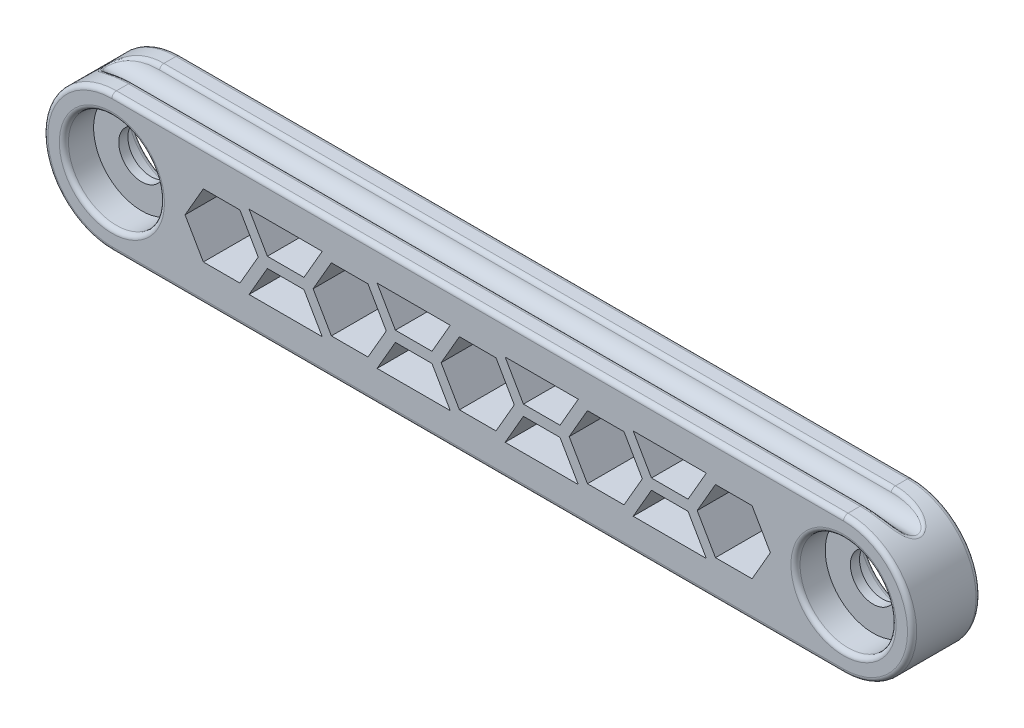
SolidWorks part; units mm, degrees
ref_plane "Front Plane" through (0, 0, 0) normal (0, 0, 1) x (1, 0, 0)
ref_plane "Top Plane" through (0, 0, 0) normal (0, 1, 0) x (1, 0, 0)
ref_plane "Right Plane" through (0, 0, 0) normal (1, 0, 0) x (0, 0, -1)
ref_axis "X" through (-88.99, 0, 0) along (1, 0, 0)
ref_axis "Y" through (0, 55, 0) along (0, -1, 0)
ref_axis "Z" through (0, 0, -88.99) along (0, 0, 1)
sketch "Sketch1" plane through (0, 0, 0) normal (0, 0, 1) x (1, 0, 0)
  line L0 (-80, 0) -> (80, 0) construction
  line L2 (-80, 15) -> (80, 15)
  line L3 (-80, -15) -> (80, -15)
  arc A0 (-80, 15) -> (-80, -15) centre (-80, 0) ccw
  arc A1 (80, -15) -> (80, 15) centre (80, 0) ccw
  circle A2 centre (80, 0) radius 10.5
  circle A3 centre (-80, 0) radius 10.5
  circle A4 centre (-80, 0) radius 5
  circle A5 centre (80, 0) radius 5
  point P5 (0, 0)
  dimension "D2" = 15
  dimension "D3" = 21
  dimension "D4" = 10
  dimension "D1" = 160
extrude "Boss-Extrude1" add sketch "Sketch1" along normal mid plane 2 contours L3 A1 L2 A0 A3 A2 | A4 A3 | A2 A5 region at (0, 0, 0) region at (69.797, 0, 0) region at (-90.203, 0, 0)
extrude "Boss-Extrude2" add sketch "Sketch1<3>" along normal mid plane 15 contours L3 A1 L2 A0 A3 A2 region at (0, 0, 0)
sketch "Sketch1<3>" plane through (0, 0, 0) normal (0, 0, 1) x (1, 0, 0) same geometry as "Sketch1"
sketch "Sketch2" plane through (0, 0, 0) normal (1, 0, 0) x (0, 0, -1)
  line L0 (-7.5, 15) -> (7.5, 15) construction
  line L1 (-7.5, 15) -> (7.5, 15)
  arc A0 (-3, 15) -> (3, 15) centre (0, 15) ccw
  point P6 (0, 15)
  dimension "D1" = 3
extrude "Cut-Extrude1" cut sketch "Sketch2" against normal through all both and the other way through all contours L1 A0 region at (0, 13.7268, 0)
fillet "Fillet1" radius 1 4 edges at (-88.9935, 12.0049, -0.1707) (0, 15, 3) (88.9935, 12.0049, 0.1707) (0, 15, -3)
mirror "Mirror3" [suppressed] about plane through (0, 0, 0) normal (0, 1, 0)
sketch "Sketch3" [suppressed] plane through (0, 0, 1) normal (0, 0, 1) x (1, 0, 0)
  circle A1 centre (80, 0) radius 11.1
  circle A2 centre (80, 0) radius 11.1
  circle A3 centre (80, 0) radius 5 construction
  circle A4 centre (80, 0) radius 5
  dimension "D1" = 0
extrude "Boss-Extrude3" [suppressed] add sketch "Sketch3" along normal up to surface (6.5 mm away) up to face at (90.5, 0, 7.5)
fillet "Fillet2" radius 1 12 edges at (-95, 0, 7.5) (0, 15, 7.5) (95, 0, 7.5) (0, -15, 7.5) (-69.5, 0, 7.5) (90.5, 0, 7.5) (95, 0, -7.5) (0, 15, -7.5) (-95, 0, -7.5) (0, -15, -7.5) (-69.5, 0, -7.5) (90.5, 0, -7.5)
mirror "Mirror1" [suppressed] about plane through (0, 0, 0) normal (1, 0, 0) of bodies 104
delete or keep bodies "Body-Delete/Keep 1" [suppressed] type keep bodies bodies 105
sketch "Sketch4" [suppressed] plane through (0, 0, 7.5) normal (0, 0, 1) x (1, 0, 0)
  circle A0 centre (70.25, 0) radius 0.75 construction
  circle A1 centre (67.25, 0) radius 0.75 construction
  circle A2 centre (64.25, 0) radius 0.75 construction
  circle A3 centre (61.25, 0) radius 0.75 construction
  circle A4 centre (70.25, 0) radius 0.75 construction
  circle A5 centre (67.25, 0) radius 0.75 construction
  circle A6 centre (64.25, 0) radius 0.75 construction
  circle A7 centre (61.25, 0) radius 0.75 construction
  circle A8 centre (61.25, 0) radius 0.6
  circle A9 centre (64.25, 0) radius 0.6
  circle A10 centre (67.25, 0) radius 0.6
  circle A11 centre (70.25, 0) radius 0.6
  circle A12 centre (92.75, 0) radius 0.75 construction
  circle A13 centre (89.75, 0) radius 0.75 construction
  circle A14 centre (92.75, 0) radius 0.75 construction
  circle A15 centre (89.75, 0) radius 0.75 construction
  circle A16 centre (89.75, 0) radius 0.6
  circle A17 centre (92.75, 0) radius 0.6
  dimension "D1" = 1.2
extrude "Cut-Extrude2" [suppressed] cut sketch "Sketch4" against normal offset from surface (6.5 mm away) 2 up to face at (85, 0, -1)
sketch "Sketch5" plane through (0, 0, 0) normal (0, 0, 1) x (1, 0, 0)
  line L0 (6, 8.0829) -> (10, 1.1547)
  line L1 (4, -6.9282) -> (8, 0)
  line L2 (8, 0) -> (4, 6.9282)
  line L3 (4, 6.9282) -> (-4, 6.9282)
  line L4 (-4, 6.9282) -> (-8, 0)
  line L5 (-8, 0) -> (-4, -6.9282)
  line L6 (-4, -6.9282) -> (4, -6.9282)
  line L7 (10, 1.1547) -> (18, 1.1547)
  line L8 (18, 1.1547) -> (22, 8.0829)
  line L9 (22, 8.0829) -> (6, 8.0829)
  line L10 (6, 3.4641) -> (8, 4.6188) construction
  line L11 (0, 0) -> (8, 0) construction
  line L12 (10, -1.1547) -> (18, -1.1547)
  line L13 (18, -1.1547) -> (22, -8.0829)
  line L14 (22, -8.0829) -> (6, -8.0829)
  line L15 (6, -8.0829) -> (10, -1.1547)
  circle A0 centre (0, 0) radius 6.9282 construction
  dimension "D1" = 8
  dimension "D2" = 2
extrude "Cut-Extrude3" cut sketch "Sketch5" against normal through all both and the other way through all contours L5 L6 L1 L2 L3 L4 region at (0, 0, 0)
extrude "Cut-Extrude4" cut sketch "Sketch5<3>" against normal through all both and the other way through all contours L15 L14 L13 L12 | L8 L9 L0 L7 region at (14, 5.0037, 0) region at (14, -5.0037, 0)
sketch "Sketch5<3>" plane through (0, 0, 0) normal (0, 0, 1) x (1, 0, 0) same geometry as "Sketch5"
pattern_linear "LPattern1" count 3 spacing 28 along (1, 0, 0) count 3 spacing 28 along (-1, 0, 0) of "Cut-Extrude3"
pattern_linear "LPattern2" count 2 spacing 28 along (1, 0, 0) count 3 spacing 28 along (-1, 0, 0) of "Cut-Extrude4"
